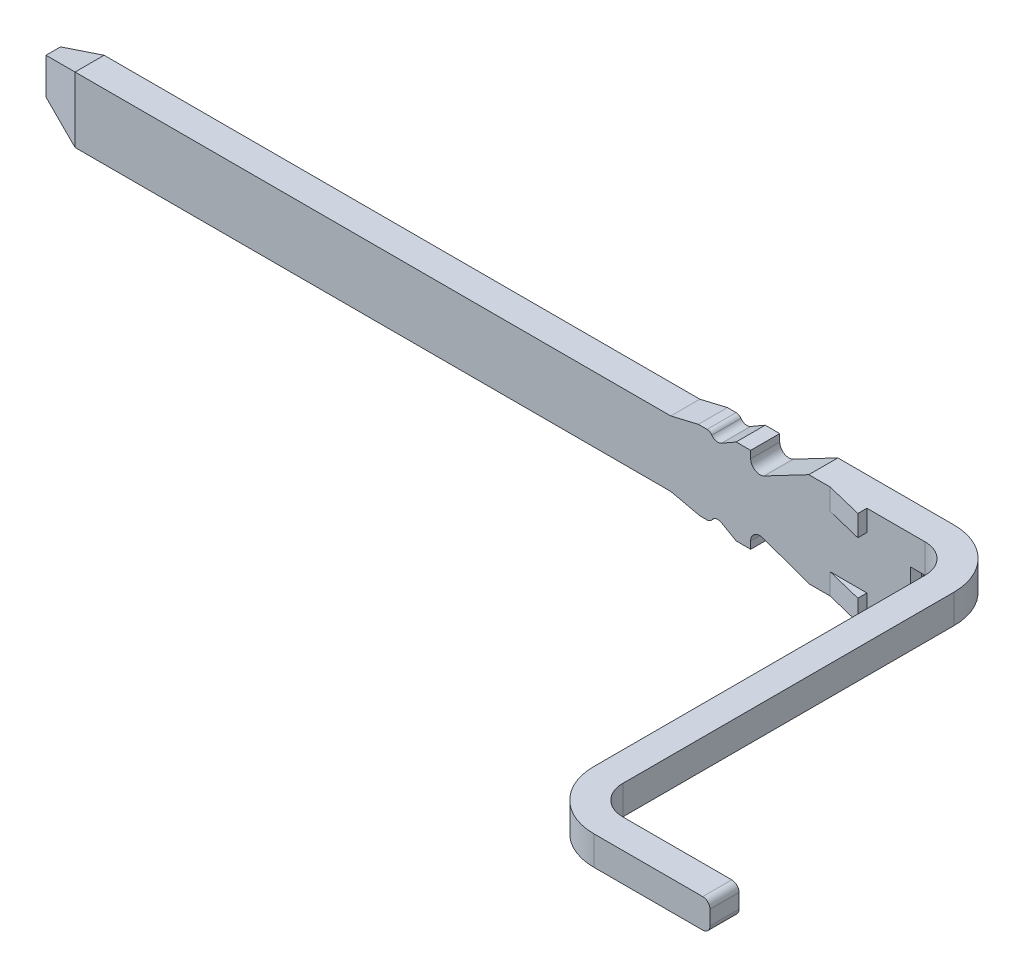
SolidWorks part; units mm, degrees
ref_plane "Plano frontal" through (0, 0, 0) normal (0, 0, 1) x (1, 0, 0)
ref_plane "Plano superior" through (0, 0, 0) normal (0, 1, 0) x (1, 0, 0)
ref_plane "Plano direito" through (0, 0, 0) normal (1, 0, 0) x (0, 0, -1)
sketch "Esboço1" plane through (0, 0, 0) normal (0, 0, 1) x (1, 0, 0)
  line L7 (76.7103, 206.6161) -> (76.7103, 206.4161)
  line L13 (75.9103, 205.9661) -> (76.082, 205.9661)
  line L14 (75.9103, 205.9661) -> (75.5955, 206.0807)
  line L15 (75.5103, 206.0211) -> (75.5103, 205.9711)
  line L16 (75.5103, 205.9711) -> (75.4103, 205.9711)
  line L17 (75.4103, 205.9711) -> (75.3099, 206.0291)
  line L18 (75.2103, 205.9961) -> (75.1603, 205.9961)
  line L19 (75.1603, 205.9961) -> (74.9603, 206.0411)
  line L20 (74.9603, 206.0411) -> (70.8603, 206.0411)
  line L21 (70.8603, 206.0411) -> (70.5603, 206.1411)
  line L22 (70.5603, 206.1411) -> (70.5603, 206.3911)
  line L23 (70.5603, 206.3911) -> (70.8603, 206.4911)
  line L24 (70.8603, 206.4911) -> (74.9603, 206.4911)
  line L25 (74.9603, 206.4911) -> (75.1503, 206.5361)
  line L26 (75.1503, 206.5361) -> (75.2103, 206.5361)
  line L27 (75.3099, 206.5031) -> (75.4103, 206.5611)
  line L28 (75.4103, 206.5611) -> (75.5103, 206.5611)
  line L29 (75.5103, 206.5611) -> (75.5103, 206.5111)
  line L30 (75.6032, 206.4549) -> (75.9103, 206.6161)
  line L35 (76.6103, 206.1161) -> (76.5603, 206.1161)
  line L36 (76.5103, 206.0661) -> (76.5103, 205.9661)
  line L37 (76.5103, 205.9661) -> (76.1103, 205.9661)
  line L38 (76.1103, 206.6161) -> (76.7103, 206.6161)
  line L39 (76.082, 206.6161) -> (75.9103, 206.6161)
  line L40 (76.7103, 206.4161) -> (76.6573, 206.4161)
  line L41 (76.6453, 206.1161) -> (76.6103, 206.1161)
  line L43 (76.1103, 205.9661) -> (76.082, 205.9661)
  line L44 (76.1103, 206.6161) -> (76.082, 206.6161)
  line L45 (76.6573, 206.1161) -> (76.6573, 206.4161)
  line L46 (76.6573, 206.1161) -> (76.6453, 206.1161)
  arc A2 (75.5955, 206.0807) -> (75.5103, 206.0211) centre (75.5738, 206.0211) ccw
  arc A3 (75.3099, 206.0291) -> (75.2435, 206.0137) centre (75.2849, 205.9858) ccw
  arc A4 (75.2103, 205.9961) -> (75.2435, 206.0137) centre (75.2103, 206.0361) ccw
  arc A5 (75.2435, 206.5185) -> (75.2103, 206.5361) centre (75.2103, 206.4961) ccw
  arc A6 (75.2435, 206.5185) -> (75.3099, 206.5031) centre (75.2849, 206.5465) ccw
  arc A7 (75.5103, 206.5111) -> (75.6032, 206.4549) centre (75.5738, 206.5111) ccw
  arc A8 (76.5603, 206.1161) -> (76.5103, 206.0661) centre (76.5603, 206.0661) ccw
extrude "Ressalto-extrusão1" add sketch "Esboço1" along normal blind 0.2
sketch "Esboço2" plane through (0, 206.4161, 0) normal (0, -1, 0) x (1, 0, 0)
  line L3 (76.7103, 0.2) -> (76.7103, 0) construction
  line L4 (76.7103, 0) -> (76.7103, 0.2)
  line L5 (76.9103, 0.4) -> (76.9103, 2.68)
  line L7 (77.1103, 0.4) -> (77.1103, 2.68)
  line L10 (77.3103, 2.88) -> (78.1103, 2.88)
  line L12 (77.3103, 3.08) -> (78.1103, 3.08)
  line L13 (78.1103, 2.88) -> (78.1103, 3.08)
  arc A0 (76.7103, 0) -> (77.1103, 0.4) centre (76.7103, 0.4) ccw
  arc A1 (76.7103, 0.2) -> (76.9103, 0.4) centre (76.7103, 0.4) ccw
  arc A2 (77.3103, 2.88) -> (77.1103, 2.68) centre (77.3103, 2.68) ccw
  arc A3 (76.9103, 2.68) -> (77.3103, 3.08) centre (77.3103, 2.68) cw
  dimension "D5" = 0.2
  dimension "D6" = 0.4
  dimension "D12" = 0.4
  dimension "D13" = 0.2
  dimension "D1" = 0.2
  dimension "D2" = 0.4
  dimension "D3" = 0.4
  dimension "D4" = 0.2
  dimension "D7" = 2.28
  dimension "D10" = 0.2
  dimension "D11" = 0.8
extrude "Ressalto-extrusão2" add sketch "Esboço2" against normal blind 0.2
sketch "Esboço3" plane through (0, 206.4911, 0) normal (0, 1, 0) x (1, 0, 0)
  line L1 (70.5603, -0.2) -> (70.5603, 0) construction
  line L2 (70.5603, -0.1) -> (70.4759, -0.1)
  line L6 (70.8603, -0.2) -> (70.5603, -0.1)
  line L7 (70.4759, -0.1) -> (70.4759, -0.2887)
  line L8 (70.4759, -0.2887) -> (70.8603, -0.2887)
  line L9 (70.8603, -0.2887) -> (70.8603, -0.2)
  dimension "D1" = 0.1
extrude "Corte-extrusão1" cut sketch "Esboço3" against normal blind 1
fillet "Filete1" radius 0.05 2 edges at (78.1103, 206.4161, 2.98) (78.1103, 206.6161, 2.98)
sketch "Esboço4" plane through (0, 206.6161, 0) normal (0, 1, 0) x (1, 0, 0)
  line L5 (76.0576, -0.2) -> (76.3103, -0.2624)
  line L6 (76.7103, -0.2) -> (75.9103, -0.2) construction
  line L7 (76.3103, -0.2624) -> (76.3103, -0.2)
  line L8 (76.3103, -0.2) -> (76.0576, -0.2)
  dimension "D4" = 0.0624
extrude "Ressalto-extrusão3" add sketch "Esboço4" against normal blind 0.145
pattern_linear "Padrão linear1" count 2 spacing 0.505 along (0, -1, 0) of "Ressalto-extrusão3"
sketch "Esboço5" plane through (0, 206.1161, 0) normal (0, -1, 0) x (1, 0, 0)
  line L0 (76.6573, 0.16) -> (76.6453, 0.16)
  line L1 (76.6573, 0.2) -> (76.6573, 0) construction
  line L2 (76.6453, 0.16) -> (76.6088, 0.2)
  line L3 (76.5603, 0.2) -> (76.6573, 0.2) construction
  line L4 (76.6088, 0.2) -> (76.6088, 0.2324)
  line L5 (76.6088, 0.2324) -> (76.6797, 0.2324)
  line L6 (76.6797, 0.2324) -> (76.6797, 0.16)
  line L7 (76.6797, 0.16) -> (76.6573, 0.16)
  line L8 (76.6088, 0) -> (76.6453, 0.04)
  line L9 (76.5603, 0) -> (76.6573, 0) construction
  line L10 (76.6453, 0.04) -> (76.6797, 0.04)
  line L11 (76.6797, 0.04) -> (76.6797, -0.0141)
  line L12 (76.6797, -0.0141) -> (76.6088, -0.0141)
  line L13 (76.6088, 0) -> (76.6088, -0.0141)
  dimension "D1" = 0.012
  dimension "D2" = 0.04
  dimension "D3" = 0.04
extrude "Corte-extrusão2" cut sketch "Esboço5" against normal up to surface (0.3 mm away) up to face at (77.1265, 206.4161, 1.54)
